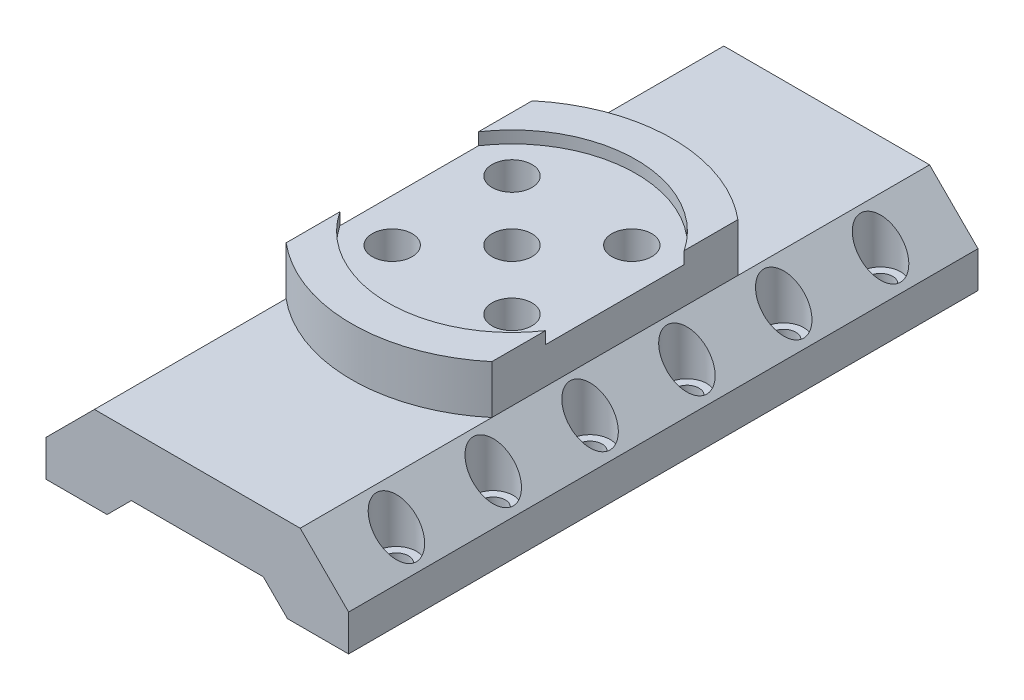
SolidWorks part; units mm, degrees
note: The reader was unsure of these and kept them because the rebuilt part matched: shared geometry of "Sketch12<3>".
ref_plane "Front Plane" through (0, 0, 0) normal (0, 0, 1) x (1, 0, 0)
ref_plane "Top Plane" through (0, 0, 0) normal (0, 1, 0) x (1, 0, 0)
ref_plane "Right Plane" through (0, 0, 0) normal (1, 0, 0) x (0, 0, -1)
sketch "Sketch1" plane through (0, 0, 0) normal (0, 1, 0) x (1, 0, 0)
  line L1 (-12.5, -26) -> (12.5, -26)
  line L2 (-12.5, -26) -> (-12.5, 26)
  line L3 (-12.5, 26) -> (12.5, 26)
  line L4 (12.5, -26) -> (12.5, 26)
  line L5 (-12.5, -26) -> (12.5, 26) construction
  line L6 (-12.5, 26) -> (12.5, -26) construction
  point P0 (0, 0)
  dimension "D1" = 25
  dimension "D2" = 52
extrude "Boss-Extrude1" add sketch "Sketch1" along normal blind 7
sketch "Sketch2" plane through (0, 7, 0) normal (0, 1, 0) x (1, 0, 0)
  line L0 (-10.45, -20) -> (10.45, -20) construction
  line L1 (-12.5, -26) -> (12.5, -26) construction
  circle A0 centre (-10.45, -20) radius 1
  circle A1 centre (10.45, -20) radius 1
  point P4 (0, -20)
  dimension "D1" = 2
  dimension "D2" = 20.9
  dimension "D3" = 6
extrude "Cut-Extrude1" cut sketch "Sketch2" against normal through all
pattern_linear "LPattern1" count 6 spacing 8 along (0, 0, -1) of "Cut-Extrude1"
chamfer "Chamfer2" distance 4 angle 45 2 edges at (-12.5, 7, 0) (12.5, 7, 0)
sketch "Sketch10" plane through (0, 0, 0) normal (0, -1, 0) x (1, 0, 0)
  line L0 (12.5, -26) -> (-12.5, -26) construction
  line L1 (-7.45, -26) -> (7.45, -26)
  line L2 (-7.45, -26) -> (-7.45, 26)
  line L3 (-7.45, 26) -> (7.45, 26)
  line L4 (7.45, -26) -> (7.45, 26)
  line L5 (-12.5, 26) -> (12.5, 26) construction
  circle A0 centre (10.45, 20) radius 1 construction
  circle A1 centre (-10.45, 20) radius 1 construction
  dimension "D1" = 3
  dimension "D2" = 3
extrude "Cut-Extrude4" cut sketch "Sketch10" against normal blind 2
chamfer "Chamfer3" distance 2 angle 45 2 edges at (7.45, 2, 0) (-7.45, 2, 0)
sketch "Sketch12" plane through (0, 7, 0) normal (0, 1, 0) x (1, 0, 0)
  line L0 (-8.5, 26) -> (-8.5, -26) construction
  line L1 (-8.5, 26) -> (-8.5, -26)
  line L2 (8.5, -26) -> (8.5, 26) construction
  line L3 (8.5, -26) -> (8.5, 26)
  circle A0 centre (0, 0) radius 10.25
  circle A1 centre (0, 0) radius 13.25
  line M3 (-8.5, 26) -> (-8.5, -26)
  line M5 (8.5, -26) -> (8.5, 26)
  dimension "D1" = 20.5
  dimension "D2" = 3
extrude "Boss-Extrude2" add sketch "Sketch12" along normal blind 3 contours A1 L1 A0 M5 | L1 A1 A0 M3 | A1 L3 A0 M3 | L3 A1 A0 M5 | L1 A0 | L3 A0
extrude "Boss-Extrude3" add sketch "Sketch12<3>" along normal blind 4 contours A1 L1 A0 M5 | A1 L3 A0 M3
sketch "Sketch12<3>" plane through (0, 7, 0) normal (0, 1, 0) x (1, 0, 0) same geometry as "Sketch12"
sketch "Sketch13" plane through (0, 10, 0) normal (0, 1, 0) x (1, 0, 0)
  line L0 (-4.9497, 4.9497) -> (0, 0) construction
  line L1 (0, 0) -> (-7, 0) construction
  circle A0 centre (0, 0) radius 7 construction
  circle A1 centre (-4.9497, 4.9497) radius 1.65
  circle A2 centre (4.9497, 4.9497) radius 1.65
  circle A3 centre (4.9497, -4.9497) radius 1.65
  circle A4 centre (-4.9497, -4.9497) radius 1.65
  circle A5 centre (0, 0) radius 1.65
  point P15 (0, 0)
  dimension "D2" = 3.3
  dimension "D3" = 14
  dimension "D1" = 45
  dimension "D4" = 4
extrude "Cut-Extrude5" cut sketch "Sketch13" against normal blind 3
sketch "Sketch14" plane through (0, 7, 0) normal (0, 1, 0) x (1, 0, 0)
  circle A0 centre (-4.9497, 4.9497) radius 3
  circle A1 centre (4.9497, 4.9497) radius 3
  circle A2 centre (4.9497, -4.9497) radius 3
  circle A3 centre (-4.9497, -4.9497) radius 3
  circle A4 centre (0, 0) radius 3
  point P12 (0, 0)
  dimension "D1" = 6
  dimension "D2" = 4
extrude "Cut-Extrude6" cut sketch "Sketch14" against normal up to next
sketch "Sketch15" plane through (0, 7, 0) normal (0, 1, 0) x (1, 0, 0)
sketch "Sketch16" plane through (0, 7, 0) normal (0, 1, 0) x (1, 0, 0)
  circle A0 centre (-10.45, -20) radius 1.65
  circle A1 centre (10.45, -20) radius 1.65
  circle A2 centre (10.45, -12) radius 1.65
  circle A3 centre (-10.45, -12) radius 1.65
  circle A4 centre (10.45, -4) radius 1.65
  circle A5 centre (-10.45, -4) radius 1.65
  circle A6 centre (10.45, 4) radius 1.65
  circle A7 centre (-10.45, 4) radius 1.65
  circle A8 centre (10.45, 12) radius 1.65
  circle A9 centre (-10.45, 12) radius 1.65
  circle A10 centre (10.45, 20) radius 1.65
  circle A11 centre (-10.45, 20) radius 1.65
  point P6 (-10.45, -12)
  dimension "D2" = 3.3
  dimension "D1" = 6
extrude "Cut-Extrude7" cut sketch "Sketch16" against normal blind 4.5
